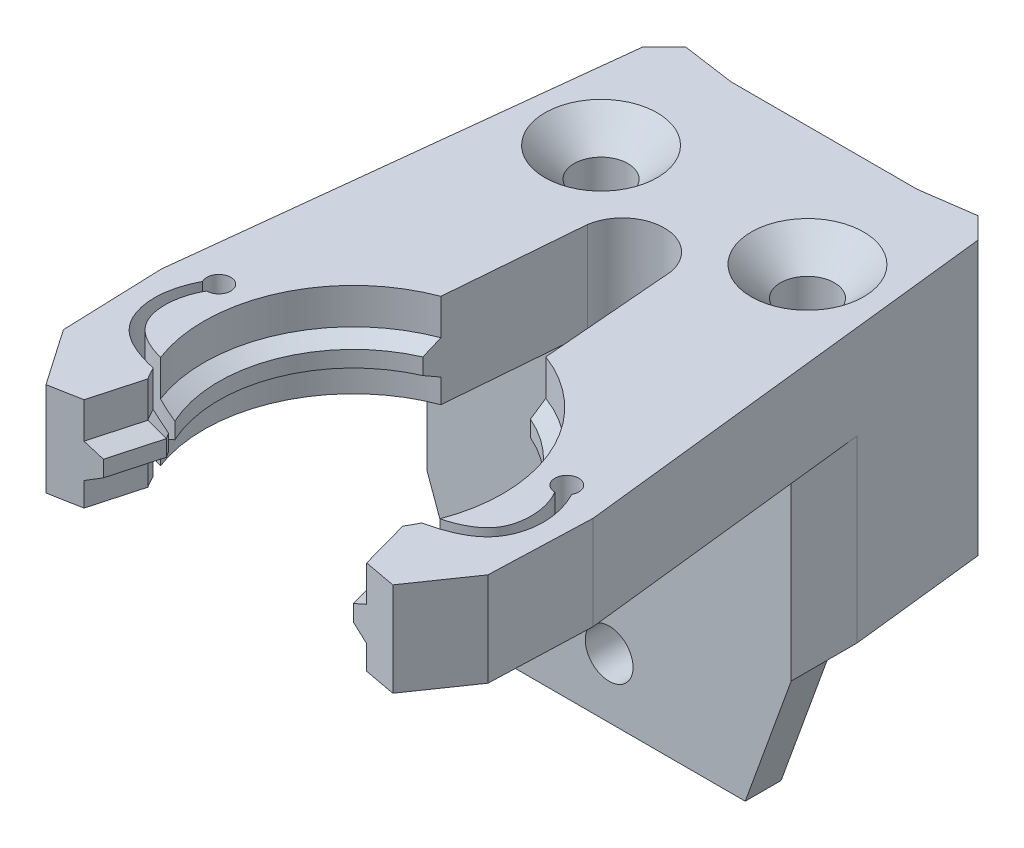
SolidWorks part; units mm, degrees
ref_plane "Спереди" through (0, 0, 0) normal (0, 0, 1) x (1, 0, 0)
ref_plane "Сверху" through (0, 0, 0) normal (0, 1, 0) x (1, 0, 0)
ref_plane "Справа" through (0, 0, 0) normal (1, 0, 0) x (0, 0, -1)
sketch "Эскиз1" plane through (0, 0, 0) normal (0, 1, 0) x (1, 0, 0)
  line L0 (19, -55.8429) -> (21.087, -30.3642)
  line L1 (7.1, -97.3641) -> (9.3855, -89.1037)
  line L2 (12.4469, 2.2759) -> (43.5531, 2.2759)
  line L3 (43.5531, 2.2759) -> (52.4645, 3.5355)
  line L4 (52.4645, 3.5355) -> (56, 0)
  line L5 (56, 0) -> (64.1, -72.4645)
  line L6 (28, 55.0682) -> (28, -135.3477) construction
  line L7 (64.1, -72.4645) -> (63.5, -89.4539)
  line L8 (63.5, -89.4539) -> (57, -98.8641)
  line L9 (57, -98.8641) -> (48.9, -97.3641)
  line L10 (48.9, -97.3641) -> (46.6145, -89.1037)
  line L11 (-1, -98.8641) -> (7.1, -97.3641)
  line L12 (37, -55.8429) -> (34.913, -30.3642)
  line L13 (-7.5, -89.4539) -> (-1, -98.8641)
  line L14 (-8.1, -72.4645) -> (-7.5, -89.4539)
  line L15 (0, 0) -> (-8.1, -72.4645)
  line L16 (3.5355, 3.5355) -> (0, 0)
  line L17 (12.4469, 2.2759) -> (3.5355, 3.5355)
  arc A0 (46.6145, -89.1037) -> (37, -55.8429) centre (28, -76.4645) ccw
  arc A1 (34.913, -30.3642) -> (21.087, -30.3642) centre (28, -31.4645) ccw
  arc A2 (9.3855, -89.1037) -> (19, -55.8429) centre (28, -76.4645) cw
  point P28 (28, 2.2759)
  dimension "D17" = 80
  dimension "D18" = 45
  dimension "D3" = 5
  dimension "D5" = 9
  dimension "D7" = 36.1
  dimension "D8" = 76
  dimension "D9" = 17
  dimension "D10" = 35.5
  dimension "D11" = 102.5
  dimension "D12" = 29
  dimension "D13" = 20.9
  dimension "D14" = 1.5
extrude "Бобышка-Вытянуть1" add sketch "Эскиз1" along normal blind 15.7
sketch "Эскиз9" plane through (0, 15.7, 0) normal (0, 1, 0) x (1, 0, 0)
  line L5 (4.6905, -96.6974) -> (6.976, -88.4371)
  line L6 (4.0704, -98.9386) -> (6.6775, -89.5162)
  line L7 (4.0704, -98.9386) -> (51.9289, -98.9361)
  line L8 (49.024, -88.4371) -> (51.3095, -96.6974)
  line L9 (49.3225, -89.5162) -> (51.9289, -98.9361)
  arc A0 (49.3225, -89.5162) -> (6.6775, -89.5162) centre (28, -76.4645) ccw
  dimension "D1" = 2.5
  dimension "D2" = 2.5
extrude "Вырез-Вытянуть5" cut sketch "Эскиз9" against normal blind 6
sketch "Эскиз10" plane through (0, 0, 0) normal (0, -1, 0) x (1, 0, 0)
  line L2 (49.024, 88.4371) -> (51.3095, 96.6974)
  line L3 (49.3225, 89.5162) -> (52.7149, 101.7769)
  line L4 (2.9824, 102.8708) -> (52.7149, 101.7769)
  line L5 (4.6905, 96.6974) -> (6.976, 88.4371)
  line L6 (2.9824, 102.8708) -> (6.6775, 89.5162)
  arc A0 (6.6775, 89.5162) -> (49.3225, 89.5162) centre (28, 76.4645) ccw
  dimension "D1" = 2.5
  dimension "D2" = 2.5
extrude "Вырез-Вытянуть6" cut sketch "Эскиз10" against normal blind 4
chamfer "Фаска2" distance 1.5 distance2 2.5 2 edges at (8.2428, 9.7, 93.2339) (6.3849, 9.7, 70.2164) first distance on face at (8.2428, 6.85, 93.2339) first distance on face at (10.2888, 6.85, 71.3448)
chamfer "Фаска3" distance 1.5 distance2 2.5 2 edges at (8.2428, 4, 93.2339) (6.3849, 4, 70.2164) first distance on face at (8.2428, 6.1, 93.2339) first distance on face at (10.2888, 6.1, 71.3448)
chamfer "Фаска4" distance 1.5 distance2 2.5 2 edges at (47.7572, 9.7, 93.2339) (49.6151, 9.7, 70.2164) first distance on face at (47.7572, 6.85, 93.2339) first distance on face at (45.7112, 6.85, 71.3448)
chamfer "Фаска5" distance 1.5 distance2 2.5 2 edges at (47.7572, 4, 93.2339) (49.6151, 4, 70.2164) first distance on face at (47.7572, 6.1, 93.2339) first distance on face at (45.7112, 6.1, 71.3448)
sketch "Эскиз11" plane through (0, 15.7, 0) normal (0, 1, 0) x (1, 0, 0)
  line L0 (46.426, -86.018) -> (46.0128, -88.3793)
  line L1 (28, -31.4645) -> (28, -74.3295) construction
  line L2 (9.574, -86.018) -> (9.9872, -88.3793)
  arc A0 (58.8627, -70.8089) -> (57.1, -71.8641) centre (57.1, -69.8641) ccw
  arc A1 (-2.8627, -70.8089) -> (-1.1, -71.8641) centre (-1.1, -69.8641) cw
  spline S0 degree 3 poles (57.1, -71.8641) (58.7386, -74.4894) (59.8901, -84.1591) (49.7984, -85.9574) (46.426, -86.018) knots 0 0 0 0 0.454203 1 1 1 1
  spline S1 degree 3 poles (58.8627, -70.8089) (60.1196, -73.2282) (61.202, -77.6732) (57.8837, -86.609) (49.906, -87.6083) (46.0128, -88.3793) knots 0 0 0 0 0.305163 0.487677 1 1 1 1
  spline S2 degree 3 poles (-2.8627, -70.8089) (-4.1196, -73.2282) (-5.202, -77.6732) (-1.8837, -86.609) (6.094, -87.6083) (9.9872, -88.3793) knots 0 0 0 0 0.305163 0.487677 1 1 1 1
  spline S3 degree 3 poles (-1.1, -71.8641) (-2.7386, -74.4894) (-3.8901, -84.1591) (6.2016, -85.9574) (9.574, -86.018) knots 0 0 0 0 0.454203 1 1 1 1
  dimension "D1" = 29
  dimension "D2" = 7
extrude "Вырез-Вытянуть7" cut sketch "Эскиз11" against normal blind 20
scale "Scale1" scale about centroid uniform scaling yes scale factor 0.5
sketch "Sketch5" plane through (0, 3.9172, 0) normal (0, -1, 0) x (1, 0, 0)
  line L0 (14.0001, 18.7828) -> (9.9501, 55.015) construction
  line L1 (15.7679, 17.015) -> (14.0001, 18.7828) construction
  line L2 (20.2236, 17.6448) -> (15.7679, 17.015) construction
  line L3 (35.7766, 17.6448) -> (20.2236, 17.6448) construction
  line L4 (40.2324, 17.015) -> (35.7766, 17.6448) construction
  line L5 (42.0001, 18.7828) -> (40.2324, 17.015) construction
  line L6 (46.0501, 55.015) -> (42.0001, 18.7828) construction
  line L8 (15.7679, 17.015) -> (14.0001, 18.7828)
  line L9 (20.2236, 17.6448) -> (15.7679, 17.015)
  line L10 (35.7766, 17.6448) -> (20.2236, 17.6448)
  line L11 (40.2324, 17.015) -> (35.7766, 17.6448)
  line L12 (42.0001, 18.7828) -> (40.2324, 17.015)
  line L16 (14.0001, 18.7828) -> (12.8225, 29.3185)
  line L17 (43.2726, 30.1667) -> (42.0001, 18.7828)
  line L19 (28.0001, 31.015) -> (43.2726, 30.1667)
  line L21 (28.0001, 31.015) -> (12.7276, 30.1667)
  line L22 (12.8225, 29.3185) -> (12.7276, 30.1667)
extrude "Boss-Extrude2" add sketch "Sketch5" along normal blind 15
sketch "Sketch2" plane through (0, 11.7672, 0) normal (0, 1, 0) x (1, 0, 0)
  line L0 (28.0001, -17.6448) -> (28.0001, -31.015)
  line L1 (35.7766, -17.6448) -> (20.2236, -17.6448) construction
  line L2 (28.0001, -31.015) -> (28.0001, -24.3299)
  line L3 (28.0001, -24.3299) -> (28.0001, -27.6725)
  line L4 (28.0001, -27.6725) -> (36.6302, -27.6725)
  line L5 (28.0001, -27.6725) -> (19.3702, -27.6725)
  arc A0 (31.4566, -33.9649) -> (24.5436, -33.9649) centre (28.0001, -34.515) ccw construction
hole_wizard "CSK for M4 Flat Head Machine Screw1" positions "3DSketch1" profile "Sketch3" countersink size "M4" standard "ANSI Metric"
sketch3d "3DSketch1"
  point P0 (19.3702, 11.7672, 27.6725)
  point P3 (36.6302, 11.7672, 27.6725)
sketch "Sketch3" plane through (19.3702, 11.7672, 27.6725) normal (1, 0, 0) x (0, 0, 1)
  line L0 (0, 0) -> (0, 30)
  line L1 (0, 30) -> (2.25, 28.6481)
  line L2 (2.25, 28.6481) -> (2.25, 2.45)
  line L3 (2.25, 2.45) -> (4.7, 0)
  line L5 (4.7, 0) -> (0, 0)
  line L6 (-2.25, 2.45) -> (-4.7, 0) construction
  line L10 (0, 30) -> (-2.25, 28.6481) construction
  line L11 (0, -6.35) -> (0, 107.95) construction
  dimension "Hole Dia." = 4.5
  dimension "Hole Depth" = 30
  dimension "Near C'Sink Dia." = 9.4
  dimension "Near C'Sink Angle" = 90
  dimension "Drill Angle" = 118
sketch "Sketch6" plane through (0, 0, 32.6725) normal (0, 0, 1) x (1, 0, 0)
  line L1 (43.2726, -11.0828) -> (43.2726, 3.9172) construction
  line L2 (12.8225, -11.0828) -> (12.8225, 3.9172)
  line L3 (43.2726, -11.0828) -> (43.2726, 3.9172)
  line L5 (16.6699, -21.7095) -> (39.4251, -21.7095)
  line L7 (43.2726, 3.9172) -> (12.8225, 3.9172)
  line L8 (12.8225, -11.0828) -> (16.6699, -21.7095)
  line L10 (43.2726, -11.0828) -> (39.4251, -21.7095)
extrude "Boss-Extrude3" add sketch "Sketch6" along normal blind 3 and the other way up to vertex (2.5057 mm away) other way up to point (43.2726, 3.9172, 30.1667)
sketch "Sketch7" plane through (43.2726, 0, 0) normal (1, 0, 0) x (0, 0, -1)
  line L0 (-32.6725, -22.263) -> (-32.6725, -12.0828) construction
  line L1 (-31.6725, -11.0828) -> (-22.6725, -11.0828) construction
  line L2 (-32.6725, -22.263) -> (-32.6725, -12.0828)
  line L3 (-31.6725, -11.0828) -> (-27.1725, -11.0828)
  line L5 (-27.1725, -11.0828) -> (-27.1725, -22.263)
  line L6 (-27.1725, -22.263) -> (-32.6725, -22.263)
  line L7 (-32.6725, -12.0828) -> (-32.6725, -11.0828)
  line L8 (-30.1667, -11.0828) -> (-35.6725, -11.0828) construction
  line L9 (-32.6725, -11.0828) -> (-31.6725, -11.0828)
extrude "Cut-Extrude1" cut sketch "Sketch7" against normal through all
sketch "Sketch8" plane through (0, 3.9172, 0) normal (0, 1, 0) x (1, 0, 0)
  line L3 (31.5965, -35.6725) -> (31.4566, -33.9649)
  line L4 (24.5436, -33.9649) -> (24.4038, -35.6725)
  line L5 (24.4038, -35.6725) -> (31.5965, -35.6725)
  line L6 (31.5965, -35.6725) -> (31.4566, -33.9649)
  line L7 (24.5436, -33.9649) -> (24.4038, -35.6725)
  line L8 (24.4038, -35.6725) -> (31.5965, -35.6725)
  arc A1 (31.4566, -33.9649) -> (24.5436, -33.9649) centre (28.0001, -34.515) ccw
  arc A2 (31.4566, -33.9649) -> (24.5436, -33.9649) centre (28.0001, -34.515) ccw
  dimension "D1" = 0
extrude "Cut-Extrude2" cut sketch "Sketch8" against normal blind 5
chamfer "Chamfer1" distance 5 angle 45 1 edges at (28.0001, -1.0828, 35.6725)
sketch "Sketch9" plane through (0, 0, 35.6725) normal (0, 0, 1) x (1, 0, 0)
  circle A0 centre (28.0475, -16.7095) radius 2
extrude "Cut-Extrude3" cut sketch "Sketch9" against normal up to next
